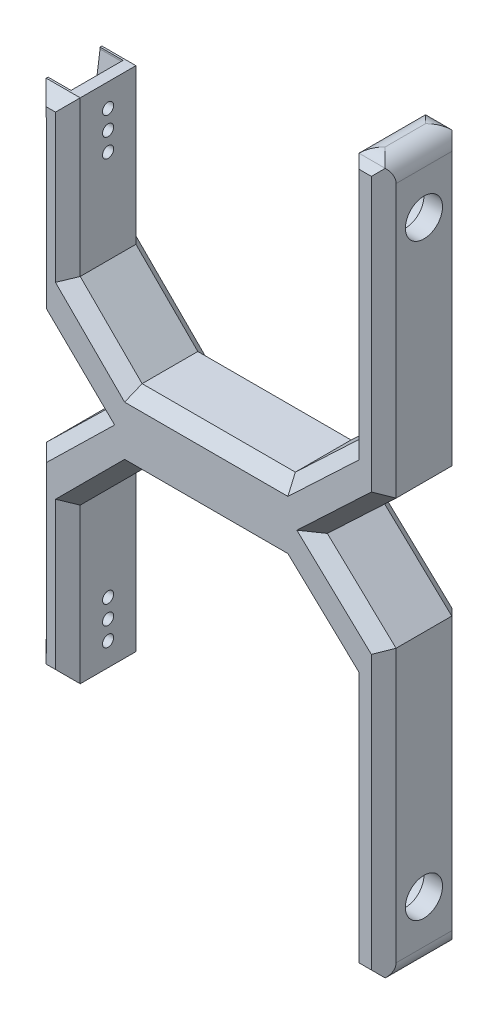
SolidWorks part; units mm, degrees
material "ABS"
ref_plane "Спереди" through (0, 0, 0) normal (0, 0, 1) x (1, 0, 0)
ref_plane "Сверху" through (0, 0, 0) normal (0, 1, 0) x (1, 0, 0)
ref_plane "Справа" through (0, 0, 0) normal (1, 0, 0) x (0, 0, -1)
sketch "Эскиз3" plane through (0, 0, 0) normal (0, 0, 1) x (1, 0, 0)
  line L0 (-15.7, 3.8984) -> (37, 3.8984) construction
  line L1 (37, -6.1016) -> (31, -6.1016)
  line L2 (31, 35.7152) -> (20.7184, 45.4255)
  line L3 (37, -6.1016) -> (37, 40.9255)
  line L4 (8.0506, 46.5729) -> (8.0506, -35.2099) construction
  line L5 (31, -6.1016) -> (31, 35.7152)
  line L6 (-14.04, 10.4255) -> (-14.04, 35.4255)
  line L7 (-19.457, 41.5459) -> (-19.54, 10.4255)
  line L8 (-19.54, 10.4255) -> (-14.04, 10.4255)
  line L9 (8.0506, 46.5729) -> (8.0506, 95.4038) construction
  line L10 (-14.04, 35.4255) -> (-4.04, 45.4255)
  line L11 (-19.457, 41.5459) -> (-9.338, 51.4255)
  line L12 (20.7184, 45.4255) -> (-4.04, 45.4255)
  line L13 (37, 40.9255) -> (25.8822, 51.4255)
  line L14 (8.0506, 56.278) -> (8.0506, 7.4471) construction
  line L15 (8.0506, 56.278) -> (8.0506, 138.0608) construction
  line L16 (-1.9494, 51.4255) -> (18.0506, 51.4255) construction
  line L17 (-15.7, 98.9525) -> (37, 98.9525) construction
  line L18 (37, 61.9255) -> (25.8822, 51.4255)
  line L19 (20.7184, 57.4255) -> (-4.04, 57.4255)
  line L20 (-19.457, 61.305) -> (-9.338, 51.4255)
  line L21 (-14.04, 67.4255) -> (-4.04, 57.4255)
  line L22 (-19.54, 92.4255) -> (-14.04, 92.4255)
  line L23 (-19.457, 61.305) -> (-19.54, 92.4255)
  line L24 (-14.04, 92.4255) -> (-14.04, 67.4255)
  line L25 (31, 108.9525) -> (31, 67.1357)
  line L26 (37, 108.9525) -> (37, 61.9255)
  line L27 (31, 67.1357) -> (20.7184, 57.4255)
  line L28 (37, 108.9525) -> (31, 108.9525)
  dimension "D1" = 35
  dimension "D2" = 6
  dimension "D3" = 6
  dimension "D5" = 5.5
  dimension "D6" = 10
extrude "Бобышка-Вытянуть3" add sketch "Эскиз3" along normal blind 13
sketch "Эскиз4" plane through (-19.5677, 0.0522, 0) normal (-1, 0.0027, 0) x (0, 0, 1)
  line L0 (9, 20.363) -> (10.5, 8.3016) construction
  line L1 (2.2577, 10.3733) -> (10.7423, 10.3733)
  line L2 (13, 10.3733) -> (0, 10.3733) construction
  line L3 (6.5, 10.3733) -> (6.5, 92.3733) construction
  line L4 (4, 20.363) -> (2.5, 8.3016) construction
  line L5 (2.2577, 10.3733) -> (3.7, 20.363)
  line L6 (10.7423, 10.3733) -> (9.3, 20.363)
  line L8 (6.5, 51.3733) -> (14.1149, 51.3733) construction
  line L9 (4, 82.3836) -> (2.5, 94.445) construction
  line L10 (9, 82.3836) -> (10.5, 94.445) construction
  line L11 (10.7019, 92.0938) -> (9.3, 82.3836)
  line L12 (2.2981, 92.0938) -> (3.7, 82.3836)
  line L14 (2.2981, 92.6528) -> (10.7019, 92.6528)
  line L15 (2.2981, 92.6528) -> (2.2981, 92.0938)
  line L17 (10.7019, 92.6528) -> (10.7019, 92.0938)
  line L18 (2.2981, 92.6528) -> (10.7019, 92.0938) construction
  line L19 (2.2981, 92.0938) -> (10.7019, 92.6528) construction
  arc A0 (9.3, 20.363) -> (3.7, 20.363) centre (6.5, 20.363) ccw
  circle A1 centre (6.5, 82.4836) radius 0.75 construction
  circle A2 centre (6.5, 85.5336) radius 0.75 construction
  circle A3 centre (6.5, 88.5836) radius 0.75 construction
  circle A4 centre (6.5, 91.6336) radius 0.75 construction
  arc A5 (4, 82.3836) -> (9, 82.3836) centre (6.5, 82.3836) ccw construction
  arc A6 (9.3, 82.3836) -> (3.7, 82.3836) centre (6.5, 82.3836) cw
  arc A7 (4, 20.363) -> (9, 20.363) centre (6.5, 20.363) cw construction
  circle A8 centre (6.5, 11.1131) radius 0.75 construction
  circle A9 centre (6.5, 14.163) radius 0.75 construction
  circle A10 centre (6.5, 17.213) radius 0.75 construction
  circle A11 centre (6.5, 20.263) radius 0.75 construction
extrude "Вырез-Вытянуть1" cut sketch "Эскиз4" against normal blind 3.5 and the other way blind 10
sketch "Эскиз5" plane through (-16.0677, 0.0428, 0) normal (-1, 0.0027, 0) x (0, 0, 1)
  line L0 (6.5, 22.8509) -> (6.5, -15.1491) construction
  line L1 (13, 51.4004) -> (0, 51.4004) construction
  circle A0 centre (6.5, 20.2509) radius 0.9
  circle A1 centre (6.5, 17.2009) radius 0.9
  circle A2 centre (6.5, 14.1509) radius 0.9
  circle A3 centre (6.5, 88.6498) radius 0.9
  circle A4 centre (6.5, 85.5998) radius 0.9
  circle A5 centre (6.5, 82.5498) radius 0.9
extrude "Вырез-Вытянуть2" cut sketch "Эскиз5" against normal blind 3.9
sketch "Эскиз7" plane through (31, 0, 0) normal (-1, 0, 0) x (0, 0, 1)
  line L0 (0, 51.4255) -> (13, 51.4255) construction
  circle A0 centre (6.5, 3.8967) radius 4.1
  circle A1 centre (6.5, 98.9542) radius 4.1
extrude "Вырез-Вытянуть3" cut sketch "Эскиз7" against normal blind 3
sketch "Эскиз8" plane through (34, 0, 0) normal (-1, 0, 0) x (0, 0, 1)
  line L0 (0, 51.4255) -> (13, 51.4255) construction
  circle A0 centre (6.5, 3.8967) radius 3
  circle A1 centre (6.5, 98.9542) radius 3
extrude "Вырез-Вытянуть4" cut sketch "Эскиз8" against normal blind 10
chamfer "Фаска1" distance 2 angle 45 44 edges at (-14.04, 22.9255, 13) (-16.79, 10.4255, 13) (-19.4985, 25.9857, 13) (-14.3975, 46.4857, 13) (-14.3975, 56.3652, 13) (-19.4985, 76.8652, 13) (-16.79, 92.4255, 13) (-14.04, 79.9255, 13) (-9.04, 62.4255, 13) (8.3392, 57.4255, 13) (25.8592, 62.2806, 13) (31, 88.0441, 13) (34, 108.9525, 13) (37, 85.439, 13) (31.4411, 56.6755, 13) (31.4411, 46.1755, 13) (37, 17.4119, 13) (34, -6.1016, 13) (31, 14.8068, 13) (25.8592, 40.5703, 13) (8.3392, 45.4255, 13) (-9.04, 40.4255, 13) (8.3392, 45.4255, 0) (25.8592, 40.5703, 0) (31, 14.8068, 0) (34, -6.1016, 0) (37, 17.4119, 0) (31.4411, 46.1755, 0) (31.4411, 56.6755, 0) (37, 85.439, 0) (34, 108.9525, 0) (31, 88.0441, 0) (25.8592, 62.2806, 0) (8.3392, 57.4255, 0) (-9.04, 62.4255, 0) (-14.04, 79.9255, 0) (-16.79, 92.4255, 0) (-19.4985, 76.8652, 0) (-14.3975, 56.3652, 0) (-14.3975, 46.4857, 0) (-19.4985, 25.9857, 0) (-16.79, 10.4255, 0) (-14.04, 22.9255, 0) (-9.04, 40.4255, 0)
fillet "Скругление1" radius 3 8 edges at (34, 108.9525, 2) (37, 108.9525, 6.5) (34, 108.9525, 11) (31, 108.9525, 6.5) (34, -6.1016, 2) (31, -6.1016, 6.5) (34, -6.1016, 11) (37, -6.1016, 6.5)
